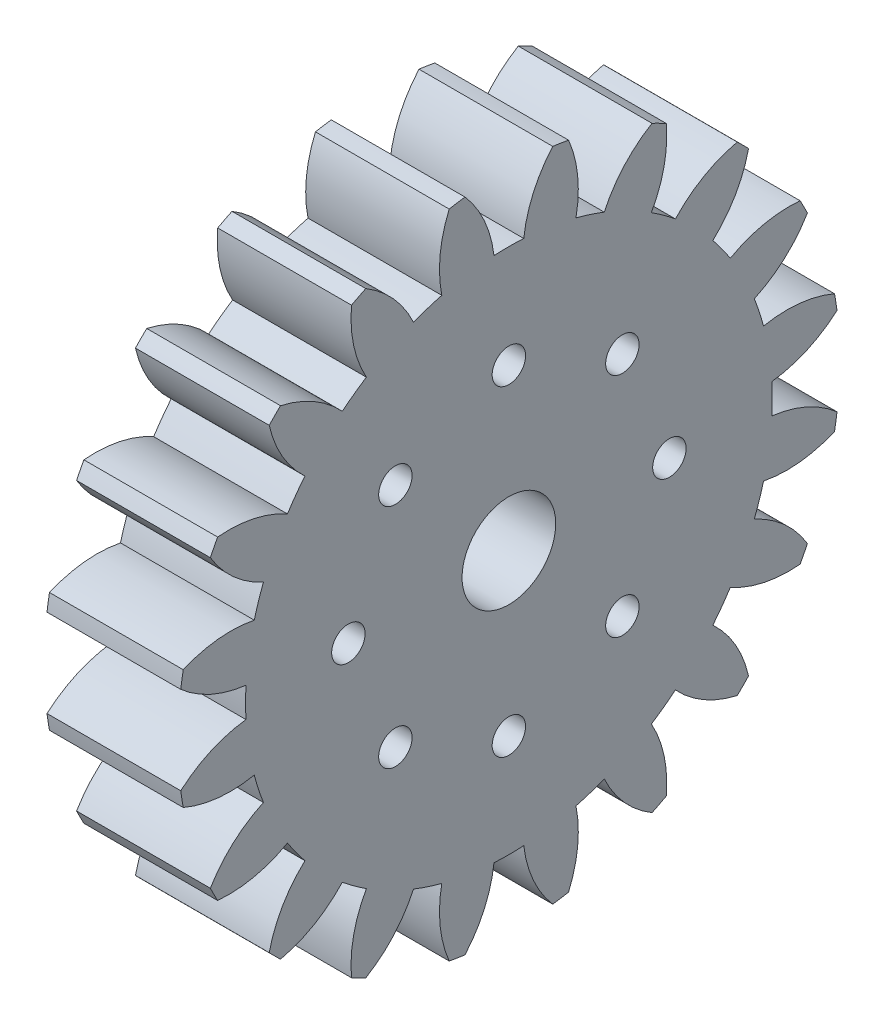
SolidWorks part; units mm, degrees
ref_plane "Plane1" through (0, 0, 0) normal (0, 0, 1) x (1, 0, 0)
ref_plane "Plane2" through (0, 0, 0) normal (0, 1, 0) x (1, 0, 0)
ref_plane "Plane3" through (0, 0, 0) normal (1, 0, 0) x (0, 0, -1)
sketch "HoldingSke" plane through (0, 0, 0) normal (0, 1, 0) x (1, 0, 0)
  line L0 (0, 0) -> (0.4176, -0.152)
  line L1 (-15, 0) -> (100, 0) construction
  line L2 (0, 0) -> (-2.1039, 2.3779)
  line L3 (0, 0) -> (-11.863, 4.5341)
  line L4 (0, 0) -> (8.1152, 2.9537)
  line L5 (0, 0) -> (-46.8476, -17.4728)
  line L6 (0, 0) -> (-8.2896, -5.593)
  line L7 (-2.1039, 2.3779) -> (8.6586, 51.2059)
  line L8 (-76.2, 54.61) -> (-72.9, 54.61)
  line L9 (-71.009, 38.7566) -> (-53.1078, 45.2721)
  line L10 (-76.2, 71.12) -> (104.1128, 71.12)
  line L11 (0, 0) -> (-10, 0)
  line L12 (-76.2, 101.6) -> (-76.123, 101.6)
  line L13 (24.9733, 27.94) -> (52.9518, 28.4284)
  line L14 (24.9733, 27.94) -> (24.9743, 27.94)
  line L15 (24.9733, 27.94) -> (100.4006, 29.5858)
  line L16 (-63.627, -2.25) -> (-12.827, -2.25)
  circle A0 centre (0, 0) radius 15
  circle A1 centre (0, 0) radius 19.6865
  circle A2 centre (0, 0) radius 37.5
  circle A3 centre (0, 0) radius 15
  dimension "Num_teeth" = 20
  dimension "Pitch_radius" = 180.3128
  dimension "Width" = 10
  dimension "Thickness" = 10
sketch "BasProSke" plane through (0, 0, 0) normal (0, 1, 0) x (1, 0, 0)
  line L0 (-10, 0) -> (60, 0) construction
  line L1 (0, 0) -> (0, 24.75)
  line L2 (0, 0) -> (10, 0)
  line L3 (10, 0) -> (10, 24.75)
  line L4 (10, 24.75) -> (0, 24.75)
  dimension "Thickness" = 10
  dimension "Diameter" = 49.5
revolve "Base-Revolve" add sketch "BasProSke" angle 360 about L0
sketch "TooCutSke" plane through (0, 0, 0) normal (1, 0, 0) x (0, 0, -1)
  line L1 (0, 0) -> (0, 107) construction
  line L2 (0, 0) -> (-1.9, 22.4196) construction
  line L3 (0, 0) -> (-7.021, 44.3291) construction
  line L4 (-1.9, 22.4196) -> (-3.5105, 22.1646) construction
  arc A0 (1.1119, 19.6551) -> (-1.1119, 19.6551) centre (0, 0) ccw
  arc A1 (3.3, 24.5546) -> (-3.3, 24.5546) centre (0, 0) ccw
  circle A2 centre (0, 0) radius 22.5 construction
  circle A3 centre (0, 0) radius 21.1431 construction
  arc A4 (-1.1119, 19.6551) -> (-3.3, 24.5546) centre (-10.0501, 18.6018) ccw
  arc A5 (3.3, 24.5546) -> (1.1119, 19.6551) centre (10.0501, 18.6018) ccw
extrude "ToothCut" cut sketch "TooCutSke" along normal through all
fillet "Breaks" [suppressed] radius 0.045 tangent propagation no
fillet "RootFillets" [suppressed] radius 0.5635
pattern_circular "TeethCuts" count 20 every 18 about axis through (-10, 0, 0) along (1, 0, 0) of "ToothCut", "RootFillets", "Breaks"
sketch "HubNeaOneSke" plane through (0, 0, 0) normal (-1, 0, 0) x (0, 0, 1)
  circle A0 centre (0, 0) radius 19.6865
  dimension "Diameter" = 39.373
extrude "HubNearOne" [suppressed] add sketch "HubNeaOneSke" along normal blind 40.0001
sketch "HubNeaBotSke" plane through (0, 0, 0) normal (-1, 0, 0) x (0, 0, 1)
  circle A0 centre (0, 0) radius 19.6865
  dimension "Diameter" = 39.373
extrude "HubNearBoth" [suppressed] add sketch "HubNeaBotSke" along normal blind 20
ref_plane "FarPln" through (10, 0, 0) normal (1, 0, 0) x (0, 0, -1)
sketch "HubFarSke" plane through (10, 0, 0) normal (1, 0, 0) x (0, 0, -1)
  circle A0 centre (0, 0) radius 19.6865
  dimension "Diameter" = 39.373
extrude "HubFar" [suppressed] add sketch "HubFarSke" along normal blind 20
sketch "BorSke" plane through (0, 0, 0) normal (1, 0, 0) x (0, 0, -1)
  circle A0 centre (0, 0) radius 15
  dimension "Diameter" = 30
extrude "Bore" cut sketch "BorSke" along normal mid plane 100.0001
sketch "KeySke" plane through (0, 0, 0) normal (1, 0, 0) x (0, 0, -1)
  line L0 (-5, 0) -> (-5, 18.3)
  line L1 (-5, 18.3) -> (5, 18.3)
  line L2 (5, 18.3) -> (5, 0)
  line L3 (0, 0) -> (0, 34) construction
  line L4 (-5, 0) -> (5, 0)
  dimension "Width" = 10
extrude "Keyway" [suppressed] cut sketch "KeySke" along normal mid plane 100.0001
pattern_circular "Keyway2" [suppressed] count 2 every 90 about axis through (-10, 0, 0) along (1, 0, 0) reverse direction yes
sketch "Sketch1" plane through (10, 0, 0) normal (1, 0, 0) x (0, 0, -1)
  circle A0 centre (0, 0) radius 15
extrude "Boss-Extrude1" add sketch "Sketch1" against normal blind 5
sketch "Sketch2" plane through (10, 0, 0) normal (1, 0, 0) x (0, 0, -1)
  circle A0 centre (0, 0) radius 3.5
  dimension "D1" = 7
extrude "Cut-Extrude1" cut sketch "Sketch2" against normal blind 5
sketch "Sketch3" plane through (10, 0, 0) normal (1, 0, 0) x (0, 0, -1)
  circle A1 centre (0, 12) radius 1.25
  circle A2 centre (8.4853, 8.4853) radius 1.25
  circle A3 centre (12, 0) radius 1.25
  circle A4 centre (8.4853, -8.4853) radius 1.25
  circle A5 centre (0, -12) radius 1.25
  circle A6 centre (-8.4853, -8.4853) radius 1.25
  circle A7 centre (-12, 0) radius 1.25
  circle A8 centre (-8.4853, 8.4853) radius 1.25
  point P21 (0, 0)
  dimension "D2" = 2.5
  dimension "D3" = 8
extrude "Cut-Extrude2" cut sketch "Sketch3" against normal blind 5
equation "' \"Module@HoldingSke\" = 6.35"
equation "' \"Num_teeth@HoldingSke\" = 12"
equation "' \"Ap@HoldingSke\" =  20"
equation "' \"Ap@HoldingSke\" = 20"
equation "' \"Width@HoldingSke\" = 0.5 * 25.4"
equation "' \"Hub_dia@HoldingSke\"= 1 * 25.4"
equation "' \"Hub_dia@HoldingSke\" = 1 * 25.4"
equation "' \"Overall_len@HoldingSke\" = 1.0 * 25.4"
equation "' \"Bore@HoldingSke\" = 0.75 * 25.4"
equation "' \"T_dim@HoldingSke\" = 0.1 * 25.4"
equation "' \"Width@KeySke\" = 0.25 * 25.4"
equation "' \"Show_teeth@HoldingSke\" = 13"
equation "' \"Backlash@HoldingSke\" = 0.009 * 25.4"
equation "' \"Addendum_fac@HoldingSke\" = 1.0"
equation "' \"Dedendum_fac@HoldingSke\" = 1.25"
equation "' \"Dedendum_add@HoldingSke\" = 0.00005 * 25.4"
equation "' \"Clearance_fac@HoldingSke\" = 0.25"
equation "\"Pitch@HoldingSke\" = 1 / \"Module@HoldingSke\""
equation "\"Overcut_dia@TooCutSke\" = (\"Num_teeth@HoldingSke\" + 2 * \"Addendum_fac@HoldingSke\") / \"Pitch@HoldingSke\" + 0.002 * 25.4"
equation "\"Pitch_dia@TooCutSke\" = \"Num_teeth@HoldingSke\" / \"Pitch@HoldingSke\""
equation "\"Base_dia@TooCutSke\" = \"Num_teeth@HoldingSke\" / \"Pitch@HoldingSke\" * cos((\"Ap@HoldingSke\"  * 3.14159265 / 180))"
equation "\"Root_dia@TooCutSke\" = (\"Num_teeth@HoldingSke\" + 2) / \"Pitch@HoldingSke\" - 2 * (\"Addendum_fac@HoldingSke\" + \"Dedendum_fac@HoldingSke\") / \"Pitch@HoldingSke\" - \"Dedendum_add@HoldingSke\" * 2"
equation "\"Half_ang@TooCutSke\" = 180 / \"Num_teeth@HoldingSke\""
equation "\"Half_CT@TooCutSke\" = \"Num_teeth@HoldingSke\" / \"Pitch@HoldingSke\" * sin((3.14159265 / 2 / \"Num_teeth@HoldingSke\")) / 2 - 7 * \"Backlash@HoldingSke\" / 4"
equation "\"Flank_rad@TooCutSke\" = \"Num_teeth@HoldingSke\" / \"Pitch@HoldingSke\" / 5"
equation "\"Radius@RootFillets\" = \"Clearance_fac@HoldingSke\" / \"Pitch@HoldingSke\" + \"Dedendum_add@HoldingSke\""
equation "\"Break_rad@Breaks\" = 0.02 / \"Pitch@HoldingSke\""
equation "\"Thickness@HoldingSke\" = \"Width@HoldingSke\""
equation "\"OAL@HoldingSke\" = \"Thickness@HoldingSke\""
equation "\"MHD@HoldingSke\" = (\"Num_teeth@HoldingSke\" + 2) / \"Pitch@HoldingSke\" - 2 * (\"Addendum_fac@HoldingSke\" + \"Dedendum_fac@HoldingSke\")  / \"Pitch@HoldingSke\" - \"Dedendum_add@HoldingSke\" * 2"
equation "\"MBD@HoldingSke\" = (\"Num_teeth@HoldingSke\" + 2) / \"Pitch@HoldingSke\" - 2 * (\"Addendum_fac@HoldingSke\" + \"Dedendum_fac@HoldingSke\")  / \"Pitch@HoldingSke\" - \"Dedendum_add@HoldingSke\" * 2 - 0.002 * 25.4"
equation "\"MHD@HoldingSke\" = ((sgn( \"MHD@HoldingSke\" - \"Hub_dia@HoldingSke\" )-1)*( \"MHD@HoldingSke\" - \"Hub_dia@HoldingSke\" ))/-2+ \"Hub_dia@HoldingSke\""
equation "\"MBD@HoldingSke\" = ((sgn( \"MBD@HoldingSke\" - \"Bore@HoldingSke\" )-1)*( \"MBD@HoldingSke\" - \"Bore@HoldingSke\" ))/-2+ \"Bore@HoldingSke\""
equation "\"OAL@HoldingSke\" = ((sgn( \"OAL@HoldingSke\" - \"Overall_len@HoldingSke\" )+1)*( \"OAL@HoldingSke\" - \"Overall_len@HoldingSke\" ))/2 + \"Overall_len@HoldingSke\" + 0.000002 * 25.4"
equation "\"Num_teeth@TeethCuts\" = int( \"Show_teeth@HoldingSke\" ) + 1"
equation "\"Num_teeth@TeethCuts\" = ((sgn( \"Num_teeth@TeethCuts\" - \"Num_teeth@HoldingSke\" )-1)*( \"Num_teeth@TeethCuts\" - \"Num_teeth@HoldingSke\" ))/-2+ \"Num_teeth@HoldingSke\""
equation "\"Num_teeth@TeethCuts\" = ((sgn( \"Num_teeth@TeethCuts\" - 2.0)+1)*( \"Num_teeth@TeethCuts\" - 2.0))/2 +2.0"
equation "\"Angle@TeethCuts\" = 360.0 / \"Num_teeth@HoldingSke\""
equation "\"Diameter@BasProSke\" = (\"Num_teeth@HoldingSke\" + 2 * \"Addendum_fac@HoldingSke\") / \"Pitch@HoldingSke\""
equation "\"Thickness@BasProSke\"  = \"Thickness@HoldingSke\""
equation "' \"Fillet_rad@BasProSke\" =  \"Thickness@HoldingSke\" * 0.05"
equation "' \"Fillet_rad@BasProSke\" = \"Thickness@HoldingSke\" * 0.05"
equation "\"MHD@HoldingSke\" = ((sgn( \"MHD@HoldingSke\" - \"Root_dia@TooCutSke\" )-1)*( \"MHD@HoldingSke\" - \"Root_dia@TooCutSke\" ))/-2+ \"Root_dia@TooCutSke\""
equation "\"Diameter@HubNeaOneSke\" = \"MHD@HoldingSke\""
equation "\"Length@HubNearOne\" = \"OAL@HoldingSke\" - \"Thickness@BasProSke\""
equation "\"Diameter@HubNeaBotSke\" = \"MHD@HoldingSke\""
equation "\"Length@HubNearBoth\" = ( \"OAL@HoldingSke\" - \"Thickness@BasProSke\" ) / 2.0"
equation "\"Thickness@FarPln\" = \"Thickness@BasProSke\""
equation "\"Diameter@HubFarSke\" = \"MHD@HoldingSke\""
equation "\"Length@HubFar\" = ( \"OAL@HoldingSke\" - \"Thickness@BasProSke\" ) / 2.0"
equation "\"Diameter@BorSke\" = \"MBD@HoldingSke\""
equation "\"D1@Bore\" = \"OAL@HoldingSke\" * 2.0"
equation "\"D1@Keyway\" = \"OAL@HoldingSke\" * 2.0"
equation "\"Offset@KeySke\" = \"T_dim@HoldingSke\" + \"MBD@HoldingSke\" / 2.0"
